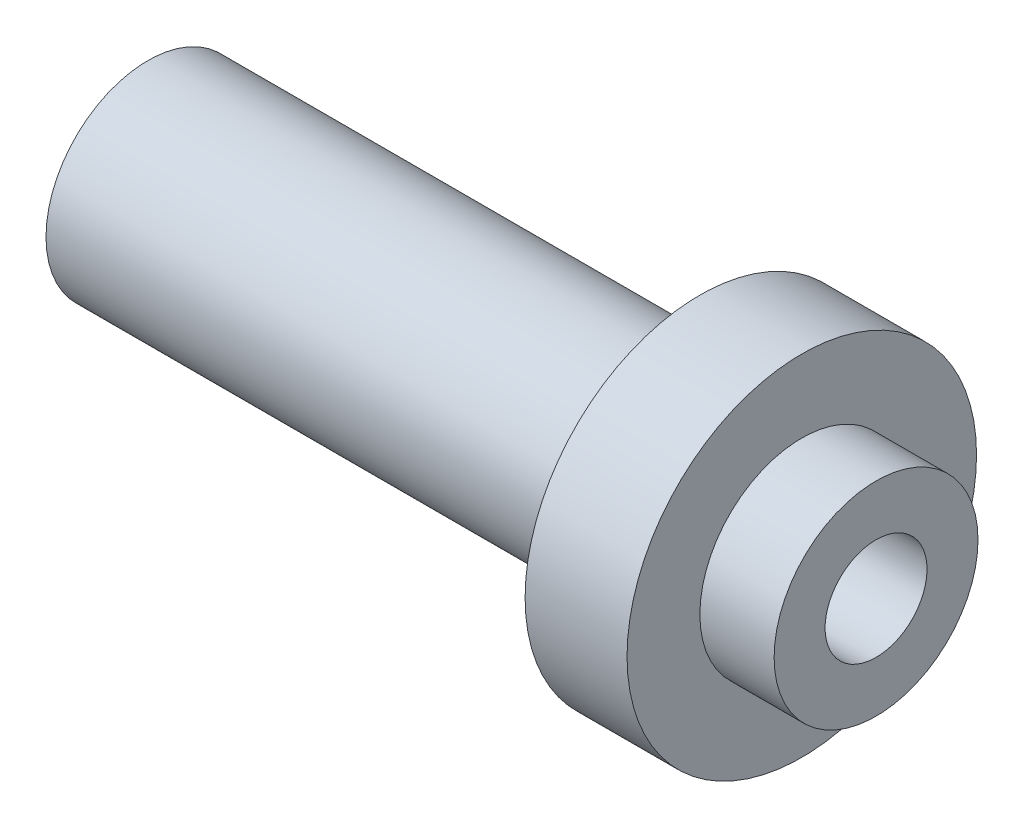
SolidWorks part; units mm, degrees
ref_plane "Front Plane" through (0, 0, 0) normal (0, 0, 1) x (1, 0, 0)
ref_plane "Top Plane" through (0, 0, 0) normal (0, 1, 0) x (1, 0, 0)
ref_plane "Right Plane" through (0, 0, 0) normal (1, 0, 0) x (0, 0, -1)
sketch "Sketch1" plane through (0, 0, 0) normal (0, 0, 1) x (1, 0, 0)
  line L0 (-5.1, 12) -> (-5.1, 7)
  line L1 (-5.1, 12) -> (-12.1, 12)
  line L2 (-12.1, 12) -> (-12.1, 7)
  line L3 (-12.1, 7) -> (-50, 7)
  line L4 (-50, 7) -> (-50, 0)
  line L5 (-78.3439, 0) -> (16.242, 0) construction
  line L6 (-5.1, 7) -> (0, 7)
  line L7 (0, 7) -> (0, 0)
  line L8 (-50, 0) -> (0, 0)
  dimension "D1" = 7
  dimension "D2" = 7
  dimension "D3" = 5
  dimension "D4" = 5.1
  dimension "D5" = 7
  dimension "D6" = 50
  dimension "D8" = 7
revolve "Revolve1" add sketch "Sketch1" angle 360 about L5
sketch "Sketch2" plane through (0, 0, 0) normal (1, 0, 0) x (0, 0, -1)
  circle A0 centre (0, 0) radius 3.5
  dimension "D1" = 7
ref_axis "Axis1" through (-5.1, 0, 0) along (-1, 0, 0)
ref_plane "Plane1" through (0, 12, 0) normal (0, 1, 0) x (1, 0, 0)
ref_plane "Plane2" through (0, 0, 12) normal (0, 0, 1) x (1, 0, 0)
hole_wizard "Trou taraudé M8x1.01" positions "Esquisse1" profile "Esquisse3" tap size "M8x1.0" standard "ISO"
sketch "Esquisse1" plane through (0, 0, 0) normal (1, 0, 0) x (0, 0, -1)
  point P0 (0, 0)
sketch "Esquisse3" plane through (0, 0, 0) normal (0, 1, 0) x (0, 0, -1)
  line L0 (0, 0) -> (0, 32.103)
  line L1 (0, 32.103) -> (3.5, 30)
  line L2 (3.5, 30) -> (3.5, 0)
  line L5 (3.5, 0) -> (0, 0)
  line L10 (0, 32.103) -> (-3.5, 30) construction
  line L11 (0, -6.35) -> (0, 107.95) construction
  dimension "Diamètre du trou pour taraudage" = 7
  dimension "Profondeur du trou pour taraudage" = 30
  dimension "Angle de pointe" = 118
cosmetic thread "Filetage de perçage1" parameters "D1"=25, "D2"=8
